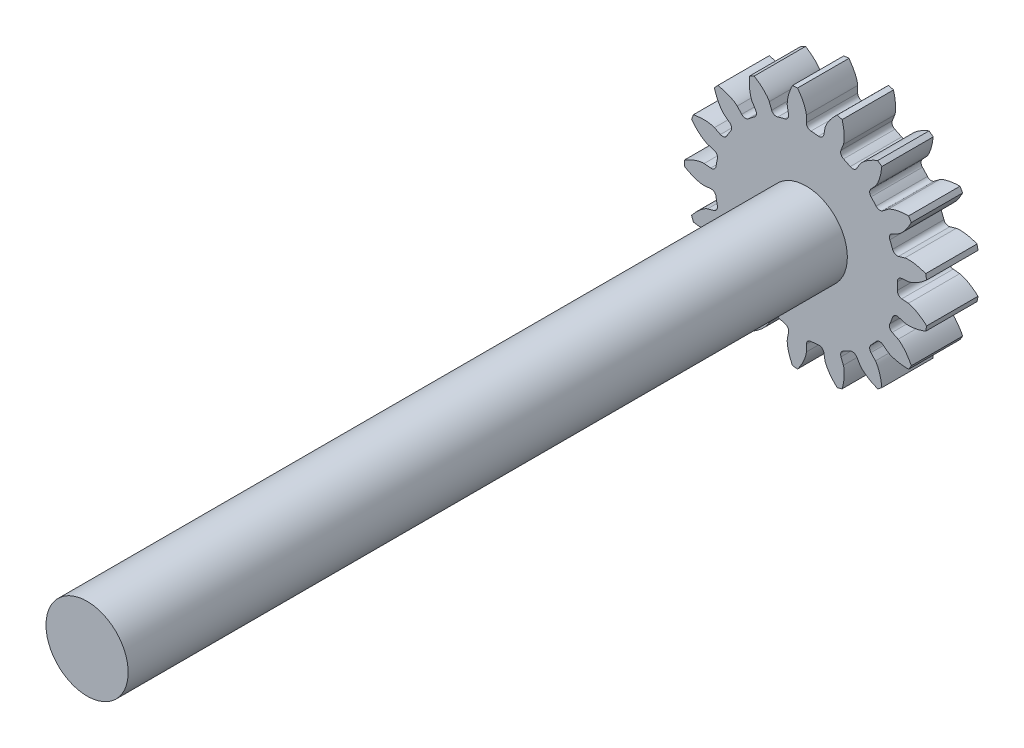
SolidWorks part; units mm, degrees
ref_plane "Front Plane" through (0, 0, 0) normal (0, 0, 1) x (1, 0, 0)
ref_plane "Top Plane" through (0, 0, 0) normal (0, 1, 0) x (1, 0, 0)
ref_plane "Right Plane" through (0, 0, 0) normal (1, 0, 0) x (0, 0, -1)
ref_axis "Gear Axis" through (0, 0, -3.7501) along (0, 0, 1)
sketch "Blank Sketch" plane through (0, 0, 0) normal (0, 0, 1) x (1, 0, 0)
  circle A0 centre (0, 0) radius 11.875
  dimension "OD" = 23.75
extrude "Blank" add sketch "Blank Sketch" along normal blind 5
sketch "Tooth Space Sketch" plane through (0, 0, 0) normal (0, 0, 1) x (1, 0, 0)
  line L0 (9.9424, 0.9134) -> (9.2988, 0.8543)
  line L1 (9.9424, -0.9134) -> (9.2988, -0.8543)
  line L2 (12.7535, 3.1007) -> (12.7535, -3.1007)
  arc A0 (9.2988, 0.8543) -> (8.8676, 0.3619) centre (9.3422, 0.3813) ccw
  arc A1 (8.8676, -0.3619) -> (9.2988, -0.8543) centre (9.3422, -0.3813) ccw
  arc A2 (8.8676, -0.3619) -> (8.8676, 0.3619) centre (0, 0) ccw
  spline S0 degree 4 poles (9.9424, 0.9134) (9.9477, 0.914) (9.9627, 0.9159) (9.9908, 0.9208) (10.0364, 0.9304) (10.094, 0.9451) (10.1679, 0.9668) (10.254, 0.9959) (10.3477, 1.0316) (10.4483, 1.0743) (10.5475, 1.1204) (10.6453, 1.1696) (10.7417, 1.2214) (10.857, 1.2875) (10.9932, 1.3713) (11.1493, 1.4758) (11.3226, 1.602) (11.4947, 1.7386) (11.6604, 1.8795) (11.8233, 2.0291) (11.9776, 2.179) (12.1329, 2.3418) (12.2737, 2.4958) (12.4257, 2.676) (12.5467, 2.8236) (12.6999, 3.0262) (12.7884, 3.1482) (12.8897, 3.2936) (12.9335, 3.3596) (12.9605, 3.4002) knots 0 0 0 0 0 0.005377 0.015084 0.028532 0.04661 0.064855 0.092111 0.119476 0.146842 0.174209 0.201575 0.228941 0.256307 0.307035 0.361767 0.4165 0.471232 0.525964 0.580697 0.635429 0.690161 0.744894 0.799626 0.854358 0.909091 0.954545 1 1 1 1 1 construction
  spline S1 degree 4 poles (9.9424, 0.9134) (9.9477, 0.914) (9.9627, 0.9159) (9.9908, 0.9208) (10.0364, 0.9304) (10.094, 0.9451) (10.1679, 0.9668) (10.254, 0.9959) (10.3477, 1.0316) (10.4483, 1.0743) (10.5475, 1.1204) (10.6453, 1.1696) (10.7417, 1.2214) (10.857, 1.2875) (10.9932, 1.3713) (11.1493, 1.4758) (11.3226, 1.602) (11.4947, 1.7386) (11.6604, 1.8795) (11.8233, 2.0291) (11.9776, 2.179) (12.1329, 2.3418) (12.2737, 2.4958) (12.4257, 2.676) (12.5467, 2.8236) (12.6667, 2.9823) (12.7243, 3.0604) (12.7535, 3.1007) knots 0 0 0 0 0 0.005377 0.015084 0.028532 0.04661 0.064855 0.092111 0.119476 0.146842 0.174209 0.201575 0.228941 0.256307 0.307035 0.361767 0.4165 0.471232 0.525964 0.580697 0.635429 0.690161 0.744894 0.799626 0.854358 0.909091 0.909091 0.909091 0.909091 0.909091
  spline S2 degree 4 poles (9.9424, -0.9134) (9.9477, -0.914) (9.9627, -0.9159) (9.9908, -0.9208) (10.0364, -0.9304) (10.094, -0.9451) (10.1679, -0.9668) (10.254, -0.9959) (10.3477, -1.0316) (10.4483, -1.0743) (10.5475, -1.1204) (10.6453, -1.1696) (10.7417, -1.2214) (10.857, -1.2875) (10.9932, -1.3713) (11.1493, -1.4758) (11.3226, -1.602) (11.4947, -1.7386) (11.6604, -1.8795) (11.8233, -2.0291) (11.9776, -2.179) (12.1329, -2.3418) (12.2737, -2.4958) (12.4257, -2.676) (12.5467, -2.8236) (12.6999, -3.0262) (12.7884, -3.1482) (12.8897, -3.2936) (12.9335, -3.3596) (12.9605, -3.4002) knots 0 0 0 0 0 0.005377 0.015084 0.028532 0.04661 0.064855 0.092111 0.119476 0.146842 0.174209 0.201575 0.228941 0.256307 0.307035 0.361767 0.4165 0.471232 0.525964 0.580697 0.635429 0.690161 0.744894 0.799626 0.854358 0.909091 0.954545 1 1 1 1 1 construction
  spline S3 degree 4 poles (9.9424, -0.9134) (9.9477, -0.914) (9.9627, -0.9159) (9.9908, -0.9208) (10.0364, -0.9304) (10.094, -0.9451) (10.1679, -0.9668) (10.254, -0.9959) (10.3477, -1.0316) (10.4483, -1.0743) (10.5475, -1.1204) (10.6453, -1.1696) (10.7417, -1.2214) (10.857, -1.2875) (10.9932, -1.3713) (11.1493, -1.4758) (11.3226, -1.602) (11.4947, -1.7386) (11.6604, -1.8795) (11.8233, -2.0291) (11.9776, -2.179) (12.1329, -2.3418) (12.2737, -2.4958) (12.4257, -2.676) (12.5467, -2.8236) (12.6667, -2.9823) (12.7243, -3.0604) (12.7535, -3.1007) knots 0 0 0 0 0 0.005377 0.015084 0.028532 0.04661 0.064855 0.092111 0.119476 0.146842 0.174209 0.201575 0.228941 0.256307 0.307035 0.361767 0.4165 0.471232 0.525964 0.580697 0.635429 0.690161 0.744894 0.799626 0.854358 0.909091 0.909091 0.909091 0.909091 0.909091
  dimension "Root" = 8.875
  dimension "Fillet" = 0.475
extrude "Tooth Space" cut sketch "Tooth Space Sketch" against normal through all both and the other way through all both
pattern_circular "Teeth" count 17 over 360 about axis through (0, 0, -3.7501) along (0, 0, 1) of "Tooth Space"
sketch "Bore Sketch" plane through (0, 0, 0) normal (0, 0, 1) x (1, 0, 0)
  circle A0 centre (0, 0) radius 4
  dimension "Bore" = 8
extrude "Bore" cut sketch "Bore Sketch" against normal through all both and the other way through all both
sketch "Sketch1" plane through (0, 0, 0) normal (0, 0, -1) x (-1, 0, 0)
  circle A1 centre (0, 0) radius 4
  circle A2 centre (0, 0) radius 4
  dimension "D1" = 0
extrude "Boss-Extrude1" add sketch "Sketch1" against normal blind 75
equation "\"No. of Teeth\"= 17"
equation "\"Module\"= 1.25"
equation "\"Bore Diameter\"= 8"
equation "\"Pressure Angle\"= 20"
equation "\"Outer Diameter\"= ( \"No. of Teeth\" + 2 ) * \"Module\""
equation "\"Pitch Diameter\"= \"No. of Teeth\" * \"Module\""
equation "\"Backlash\"= IIF ( \"Module\" <= 1 , 0.3 * \"Module\" , 0.3 )"
equation "\"Arc Length\"= ( ( \"Module\" * pi ) / 2 + \"Backlash\" )"
equation "\"Fillet Radius\"= 0.38 * \"Module\""
equation "\"Tooth Depth\"= IIF ( \"Module\" <= 1.25 , \"Module\" * 2.4 , \"Module\" * 2.25 )"
equation "\"Face Width\"= 5"
equation "\"Root Diameter\"= \"Outer Diameter\" - 2 * \"Tooth Depth\""
equation "\"Base Diameter\"= \"Pitch Diameter\" * cos ( \"Pressure Angle\" )"
equation "\"Base Radius\"= \"Base Diameter\" / 2"
equation "\"Tooth Thickness\"= \"Module\" * pi - \"Arc Length\""
equation "\"Half Space Angle\"= ( \"Arc Length\" / \"Pitch Diameter\" ) * 180 / pi"
equation "\"Involute Fn\"= tan ( \"Pressure Angle\" ) - \"Pressure Angle\" * pi / 180"
equation "\"Flank Offset\"= \"Arc Length\" / \"Pitch Diameter\" - \"Involute Fn\""
equation "\"Tip Cap Diameter\"= \"Outer Diameter\" + 2 * \"Module\""
equation "\"Flank Start Diameter\"= IIF ( \"Base Diameter\" >= ( \"Root Diameter\" + 3 * \"Fillet Radius\" ) , \"Base Diameter\" , \"Root Diameter\" + 3 * \"Fillet Radius\" )"
equation "\"Involute t1\"= ( abs ( ( \"Flank Start Diameter\" / \"Base Diameter\" ) ^ 2 - 1 ) ) ^ 0.5"
equation "\"Involute t2\"= ( abs ( ( \"Tip Cap Diameter\" / \"Base Diameter\" ) ^ 2 - 1 ) ) ^ 0.5"
equation "\"Flank Arc Radius\"= ( \"Pitch Diameter\" / 2 ) * sin ( \"Pressure Angle\" )"
equation "\"Flank Centre Angle\"= \"Half Space Angle\" + \"Pressure Angle\""
equation "\"OD@Blank Sketch\"= \"Outer Diameter\""
equation "\"Width@Blank\"= \"Face Width\""
equation "\"Root@Tooth Space Sketch\"= \"Root Diameter\" / 2"
equation "\"Fillet@Tooth Space Sketch\"= \"Fillet Radius\""
equation "\"Count@Teeth\"= \"No. of Teeth\""
equation "\"Bore@Bore Sketch\"= \"Bore Diameter\""
